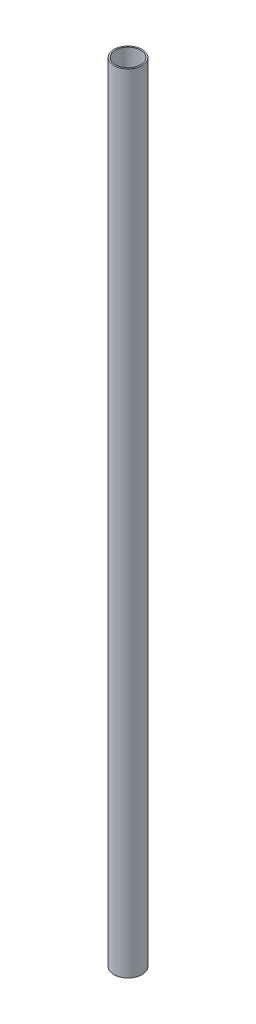
SolidWorks part; units mm, degrees
ref_plane "Front Plane" through (0, 0, 0) normal (0, 0, 1) x (1, 0, 0)
ref_plane "Top Plane" through (0, 0, 0) normal (0, 1, 0) x (1, 0, 0)
ref_plane "Right Plane" through (0, 0, 0) normal (1, 0, 0) x (0, 0, -1)
sketch "Sketch1" plane through (0, 0, 0) normal (0, 1, 0) x (1, 0, 0)
  circle A0 centre (0, 0) radius 6.35
  circle A1 centre (0, 0) radius 5.715
extrude "Boss-Extrude1" add sketch "Sketch1" along normal blind 355.6
